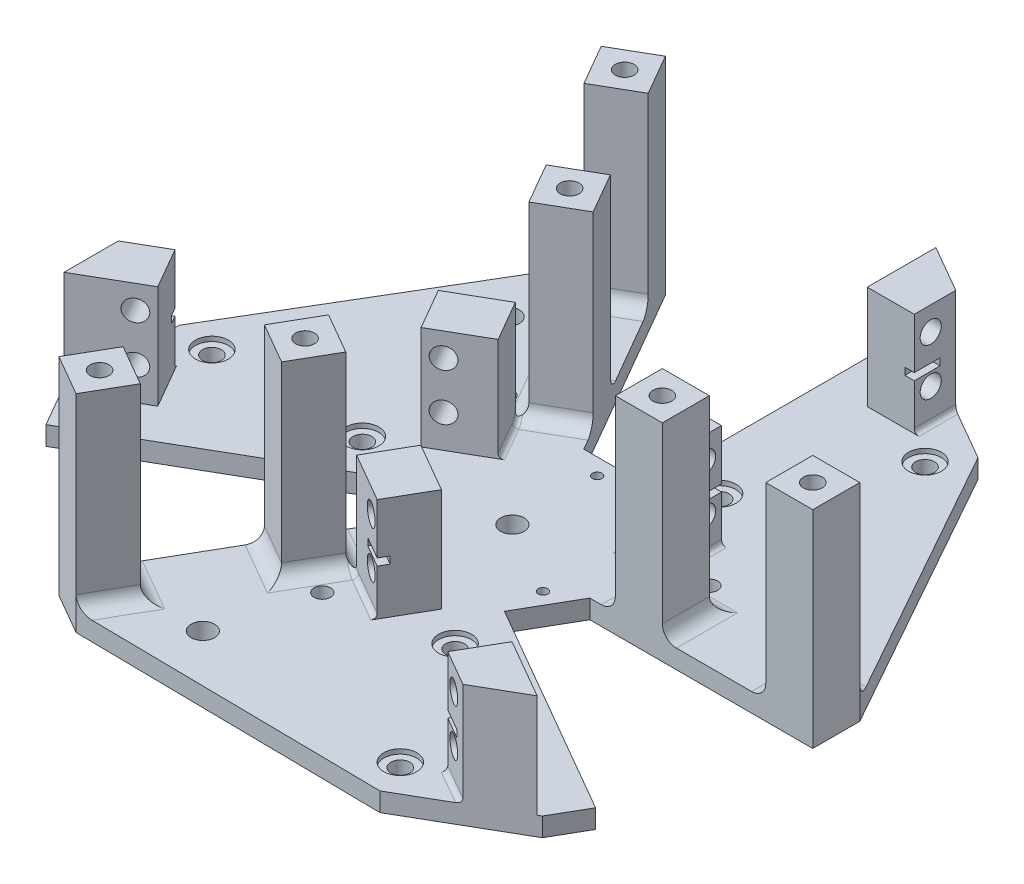
SolidWorks part; units mm, degrees
ref_plane "Front Plane" through (0, 0, 0) normal (0, 0, 1) x (1, 0, 0)
ref_plane "Top Plane" through (0, 0, 0) normal (0, 1, 0) x (1, 0, 0)
ref_plane "Right Plane" through (0, 0, 0) normal (1, 0, 0) x (0, 0, -1)
sketch "Sketch1" plane through (0, 0, 0) normal (0, 1, 0) x (1, 0, 0)
  line L19 (144.3376, 0) -> (72.1688, 125) construction
  line L20 (72.1688, 125) -> (-72.1688, 125) construction
  line L21 (-72.1688, 125) -> (-144.3376, 0) construction
  line L22 (-144.3376, 0) -> (-72.1688, -125) construction
  line L23 (-72.1688, -125) -> (72.1688, -125) construction
  line L24 (72.1688, -125) -> (144.3376, 0) construction
  line L27 (-72.1688, -125) -> (144.3376, 0)
  line L28 (-72.1688, -125) -> (-72.1688, 125)
  line L29 (-72.1688, 125) -> (144.3376, 0)
  circle A1 centre (0, 0) radius 2.5
  circle A22 centre (0, 0) radius 125 construction
  point P16 (0, 0)
  point P22 (0, 0)
  point P23 (0, 0)
  point P27 (0, 0)
  dimension "D1" = 250
  dimension "D2" = 5
extrude "Boss-Extrude1" add sketch "Sketch1" along normal blind 4 contours L20 A1 region at (-68.8616, 0, 0)
sketch "Sketch2" plane through (0, 4, 0) normal (0, 1, 0) x (1, 0, 0)
  line L0 (26, 18.5) -> (26, 6.5)
  line L1 (21, 18.5) -> (21, 59.5) construction
  line L3 (16, 74.0957) -> (16, 59.5)
  line L4 (16, 6.5) -> (26, 6.5)
  line L5 (26, 68.3222) -> (26, 59.5)
  line L26 (16, 18.5) -> (26, 18.5)
  line L28 (16, 59.5) -> (26, 59.5)
  line L29 (16, 18.5) -> (16, 6.5)
  line L50 (-72.1688, 125) -> (144.3376, 0) construction
  line L51 (16, 74.0957) -> (26, 68.3222)
  line L52 (3.0215, -31.7667) -> (-7.3708, -25.7667)
  line L53 (-2.3708, -17.1064) -> (-7.3708, -25.7667)
  line L54 (8.0215, -23.1064) -> (-2.3708, -17.1064)
  line L55 (8.0215, -23.1064) -> (3.0215, -31.7667)
  line L56 (56.1688, -50.9043) -> (43.5285, -43.6064)
  line L57 (43.5285, -43.6064) -> (38.5285, -52.2667)
  line L58 (46.1688, -56.6778) -> (38.5285, -52.2667)
  line L59 (56.1688, -50.9043) -> (46.1688, -56.6778)
  line L60 (-29.0215, 13.2667) -> (-18.6292, 19.2667)
  line L61 (-13.6292, 10.6064) -> (-18.6292, 19.2667)
  line L62 (-24.0215, 4.6064) -> (-13.6292, 10.6064)
  line L63 (-24.0215, 4.6064) -> (-29.0215, 13.2667)
  line L64 (-72.1688, -23.1915) -> (-59.5285, -15.8936)
  line L65 (-59.5285, -15.8936) -> (-64.5285, -7.2333)
  line L66 (-72.1688, -11.6445) -> (-64.5285, -7.2333)
  line L67 (-72.1688, -23.1915) -> (-72.1688, -11.6445)
  dimension "D2" = 16
  dimension "D3" = 3
  dimension "D4" = 10
  dimension "D10" = 41
  dimension "D11" = 12
extrude "Boss-Extrude2" add sketch "Sketch2" along normal blind 22 contours L26 L3 L4 L5 | L3 L28 L5 region at (21, 4, -12.5) region at (20.5891, 4, -65.4731)
sketch "Sketch3" plane through (26, 0, 0) normal (1, 0, 0) x (0, 0, -1)
  line L0 (6.5, 26) -> (6.5, 4) construction
  line L1 (15, 21) -> (63, 21) construction
  line L2 (15, 21) -> (15, 11) construction
  line L3 (15, 11) -> (63, 11) construction
  line L4 (63, 21) -> (63, 11) construction
  line L7 (68.3222, 4) -> (59.5, 4) construction
  circle A0 centre (15, 21) radius 2.25
  circle A1 centre (63, 21) radius 2.25
  circle A2 centre (15, 11) radius 2.25
  circle A3 centre (63, 11) radius 2.25
  dimension "D4" = 4.5
  dimension "D1" = 7
  dimension "D2" = 10
  dimension "D3" = 48
  dimension "D5" = 8.5
extrude "Cut-Extrude1" cut sketch "Sketch3" against normal blind 12 contours A0 | A1 | A2 | A3 region at (26, 21, -15) region at (26, 21, -63) region at (26, 11, -15) region at (26, 11, -63)
sketch "Sketch5" plane through (0, 4, 0) normal (0, 1, 0) x (1, 0, 0)
  line L0 (-72.1688, 1.2882) -> (-14.0152, 34.8632)
  line L1 (-72.1688, -125) -> (-72.1688, 125) construction
  line L2 (0, 0) -> (-15.6126, -8.9581) construction
  line L10 (-72.1688, 125) -> (16, 74.0957) construction
  line L11 (15.2998, 74.5) -> (-72.1688, 125)
  line L12 (-72.1688, 125) -> (-72.1688, 1.2882)
  line L35 (7, 21.5) -> (7, 74.5)
  line L36 (7, 74.5) -> (15.2998, 74.5)
  line L51 (-14.0152, 34.8632) -> (-6.3, 21.5)
  line L52 (-6.3, 21.5) -> (7, 21.5)
  line L53 (0, 0) -> (15.8487, -28.0296) construction
  line L54 (21.7695, -5.294) -> (15.1195, -16.8122)
  line L55 (-30.0152, 62.576) -> (-14.0152, 34.8632)
  line L77 (15.1195, -16.8122) -> (61.0189, -43.3122)
  line L78 (61.0189, -43.3122) -> (56.869, -50.5)
  line L86 (56.869, -50.5) -> (144.3376, 0)
  line L87 (144.3376, 0) -> (37.2, 61.8559)
  line L88 (-30.0152, 62.576) -> (-38.6755, 57.576)
  line L89 (-38.6755, 57.576) -> (-72.1688, 1.2882)
  line L90 (37.2, 61.8559) -> (37.2, -5.294)
  line L91 (37.2, -5.294) -> (21.7695, -5.294)
  line L92 (69.2, -5.294) -> (69.2, 4.706)
  line L93 (69.2, 4.706) -> (37.2, 61.8559)
  line L94 (69.2, -5.294) -> (37.2, -5.294)
  line L95 (-15.4695, -16.206) -> (-22.1195, -4.6878)
  line L96 (-22.1195, -4.6878) -> (-68.0189, -31.1878)
  line L97 (-68.0189, -31.1878) -> (-72.1688, -24)
  line L98 (-72.1688, -24) -> (-72.1688, -125)
  line L99 (-72.1688, -125) -> (34.9688, -63.1441)
  line L100 (34.9688, -63.1441) -> (-23.1848, -29.5691)
  line L101 (-23.1848, -29.5691) -> (-15.4695, -16.206)
  line L102 (-39.1848, -57.2819) -> (-30.5245, -62.2819)
  line L103 (-30.5245, -62.2819) -> (34.9688, -63.1441)
  line L104 (-39.1848, -57.2819) -> (-23.1848, -29.5691)
  circle A0 centre (0, 0) radius 18 construction
  circle A2 centre (-15.6126, -8.9581) radius 1
  circle A3 centre (0.0483, 17.9999) radius 1
  circle A4 centre (15.5642, -9.0418) radius 1
  circle A5 centre (15.8487, -28.0296) radius 2
  circle A6 centre (15.8487, -28.0296) radius 3.5
  circle A7 centre (-32.1987, 0.2894) radius 2
  circle A8 centre (-32.1987, 0.2894) radius 3.5
  circle A9 centre (16.35, 27.7402) radius 2
  circle A10 centre (16.35, 27.7402) radius 3.5
  point P37 (0, 0)
  point P46 (0, 0)
  point P52 (0, 0)
  point P53 (0, 0)
  point P55 (0, 0)
  point P58 (0, 0)
  point P60 (0, 0)
  line M27 (144.3376, 0) -> (26, 68.3222)
  line M28 (-72.1688, 125) -> (-72.1688, -125)
  line M29 (-72.1688, -125) -> (144.3376, 0)
  line M180 (16, 74.0957) -> (-72.1688, 125)
  dimension "D3" = 36
  dimension "D4" = 2
  dimension "D7" = 4
  dimension "D10" = 7
  dimension "D2" = 3
  dimension "D6" = 13.3
  dimension "D8" = 32.2
  dimension "D9" = 32
  dimension "D12" = 10
  dimension "D5" = 3
  dimension "D11" = 3
extrude "Cut-Extrude6" cut sketch "Sketch5" against normal through all contours L55 L51 L52 L35 L36 M180 M28 | M29 M27 | M28 M29 | A7 | A2 | A9 | A5 | A3 | A4 region at (-37.6186, 4, -67.9163) region at (77.6265, 4, 1.3794) region at (-40.0079, 4, 66.5368) region at (-15.6126, 4, 8.9581) region at (15.8487, 4, 28.0296) region at (-32.1987, 4, -0.2894) region at (16.35, 4, -27.7402)
sketch "Sketch20" plane through (0, 4, 0) normal (0, 1, 0) x (1, 0, 0)
  line L4 (-30.0152, 62.576) -> (-25.0152, 53.9157)
  line L5 (-17.6755, 21.2029) -> (-14.0152, 34.8632) construction
  line L6 (-15.8454, 28.033) -> (-24.5056, 23.033) construction
  line L7 (37.2, -5.294) -> (37.2, 4.706)
  line L8 (37.2, -5.294) -> (27.2, -5.294)
  line L9 (27.2, -5.294) -> (27.2, 4.706)
  line L10 (37.2, 4.706) -> (27.2, 4.706)
  line L11 (-23.1848, -29.5691) -> (-14.5245, -34.5691)
  line L12 (-23.1848, -29.5691) -> (-18.1848, -20.9089)
  line L13 (-18.1848, -20.9089) -> (-9.5245, -25.9089)
  line L14 (-14.5245, -34.5691) -> (-9.5245, -25.9089)
  line L17 (-17.6755, 21.2029) -> (-9.0152, 26.2029)
  line L18 (-17.6755, 21.2029) -> (-22.6755, 29.8632)
  line L19 (-9.0152, 26.2029) -> (-14.0152, 34.8632)
  line L20 (-22.6755, 29.8632) -> (-14.0152, 34.8632)
  line L21 (-14.0152, 34.8632) -> (-6.3, 21.5) construction
  line L22 (-30.0152, 62.576) -> (-38.6755, 57.576)
  line L23 (-25.0152, 53.9157) -> (-33.6755, 48.9157)
  line L24 (-38.6755, 57.576) -> (-33.6755, 48.9157)
  line L25 (-30.0152, 62.576) -> (-6.3, 21.5) construction
  line L26 (-30.0152, 62.576) -> (-33.6755, 48.9157) construction
  line L27 (69.2, -5.294) -> (59.2, -5.294)
  line L28 (69.2, -5.294) -> (69.2, 4.706)
  line L29 (69.2, 4.706) -> (59.2, 4.706)
  line L30 (59.2, -5.294) -> (59.2, 4.706)
  line L31 (-39.1848, -57.2819) -> (-34.1848, -48.6217)
  line L32 (-39.1848, -57.2819) -> (-30.5245, -62.2819)
  line L33 (-30.5245, -62.2819) -> (-25.5245, -53.6217)
  line L34 (-34.1848, -48.6217) -> (-25.5245, -53.6217)
  line L35 (-38.6755, 57.576) -> (-72.1688, 1.2882) construction
  circle A0 centre (-15.8454, 28.033) radius 2
  circle A1 centre (-24.5056, 23.033) radius 1.75
  circle A2 centre (32.2, 9.706) radius 1.75
  circle A3 centre (32.2, -0.294) radius 2
  circle A4 centre (-7.6944, -32.739) radius 1.75
  circle A5 centre (-16.3546, -27.739) radius 2
  circle A6 centre (-31.8454, 55.7459) radius 2
  circle A7 centre (64.2, -0.294) radius 2
  circle A8 centre (-32.3546, -55.4518) radius 2
  circle A9 centre (-38.8056, 37.8014) radius 2.5
  circle A10 centre (52.1398, 14.706) radius 2.5
  circle A11 centre (-13.3342, -52.5074) radius 2.5
  point P30 (0, 0)
  point P51 (0, 0)
  line M108 (-6.3, 21.5) -> (-30.0152, 62.576)
  line M155 (69.2, -5.294) -> (69.2, 4.706)
  line M157 (-30.0152, 62.576) -> (-38.6755, 57.576)
  line M162 (-15.4695, -16.206) -> (-39.1848, -57.2819)
  line M163 (-39.1848, -57.2819) -> (-30.5245, -62.2819)
  line M168 (21.7695, -5.294) -> (69.2, -5.294)
  dimension "D3" = 4
  dimension "D4" = 3.5
  dimension "D9" = 4
  dimension "D11" = 5
  dimension "D1" = 10
  dimension "D2" = 10
  dimension "D5" = 10
  dimension "D7" = 10
  dimension "D8" = 10
  dimension "D12" = 20
  dimension "D13" = 10
  dimension "D6" = 3
  dimension "D10" = 3
extrude "Boss-Extrude10" add sketch "Sketch20" along normal blind 40 contours L18 L17 A0 | L10 L9 A3 | L14 L13 A5 | L24 L23 A6 M157 M108 | L30 L29 A7 M168 M155 | L34 L33 A8 M162 M163 region at (-11.6825, 4, -30.4364) region at (-27.6825, 4, -58.1493) region at (32.2, 4, 5.1526) region at (59.3414, 4, 0.294) region at (-20.5175, 4, 25.3356) region at (-29.9512, 4, 51.289)
sketch "Sketch17" plane through (26, 0, 0) normal (1, 0, 0) x (0, 0, -1)
  line L5 (15, 19) -> (15, 9) construction
  line L6 (18.5, 26) -> (18.5, 4) construction
  line L7 (13, 13.75) -> (24, 13.75)
  line L8 (13, 13.75) -> (13, 15.25)
  line L9 (13, 15.25) -> (24, 15.25)
  line L10 (24, 13.75) -> (24, 15.25)
  line L11 (13, 13.75) -> (24, 15.25) construction
  line L12 (13, 15.25) -> (24, 13.75) construction
  line L13 (59.5, 26) -> (59.5, 4) construction
  line L14 (54, 13.75) -> (65, 13.75)
  line L15 (54, 13.75) -> (54, 15.25)
  line L16 (54, 15.25) -> (65, 15.25)
  line L17 (65, 13.75) -> (65, 15.25)
  line L18 (54, 13.75) -> (65, 15.25) construction
  line L19 (54, 15.25) -> (65, 13.75) construction
  point P2 (18.5, 14.5)
  point P11 (59.5, 14.5)
  dimension "D1" = 1.5
  dimension "D2" = 11
  dimension "D3" = 1.5
  dimension "D4" = 11
extrude "Cut-Extrude9" cut sketch "Sketch17" against normal blind 2 contours L9 L8 L7 | L14 L17 L16 L15 | L7 L10 L9 region at (26, 14.5, -18.5) region at (26, 14.5, -59.5)
pattern_circular "CirPattern5" count 3 over 360 about axis through (0, 4, 0) along (0, 1, 0) of "Boss-Extrude2", "Cut-Extrude1", "Cut-Extrude9"
extrude "Cut-Extrude10" cut sketch "Sketch20<3>" against normal blind 10 contours A1 | A0 | A2 | A3 | A4 | A5 | A9 | A10 | A11 region at (-15.8454, 4, -28.033) region at (-24.5056, 4, -23.033) region at (32.2, 4, -9.706) region at (32.2, 4, 0.294) region at (-7.6944, 4, 32.739) region at (-16.3546, 4, 27.739) region at (-38.8056, 4, -37.8014) region at (52.1398, 4, -14.706) region at (-13.3342, 4, 52.5074)
sketch "Sketch20<3>" plane through (0, 4, 0) normal (0, 1, 0) x (1, 0, 0) same geometry as "Sketch20"
extrude "Cut-Extrude11" cut sketch "Sketch5<3>" against normal blind 1 contours A8 A7 | A10 A9 | A6 A5 region at (12.4477, 4, 28.0296) region at (-35.5997, 4, -0.2894) region at (12.949, 4, -27.7402)
sketch "Sketch5<3>" plane through (0, 4, 0) normal (0, 1, 0) x (1, 0, 0) same geometry as "Sketch5"
sketch "Sketch22" plane through (0, 4, 0) normal (0, 1, 0) x (1, 0, 0)
  line L0 (69.2, 4.706) -> (37.2, 61.8559) construction
  line L1 (26, 68.3222) -> (37.2, 61.8559) construction
  circle A1 centre (64.2, -0.294) radius 2 construction
  circle A2 centre (-32.3546, -55.4518) radius 2 construction
  circle A4 centre (64.2, -0.294) radius 2
  circle A5 centre (-32.3546, -55.4518) radius 2
  circle A6 centre (-31.8454, 55.7459) radius 2 construction
  circle A7 centre (-31.8454, 55.7459) radius 2
  circle A8 centre (32.2991, 55.4825) radius 2
  circle A9 centre (32.2991, 55.4825) radius 3.5
  circle A10 centre (31.8459, -55.682) radius 3.5
  circle A11 centre (31.8459, -55.682) radius 2
  circle A12 centre (-64.1988, 0.2927) radius 3.5
  circle A13 centre (-64.1988, 0.2927) radius 2
  point P25 (-0.0179, 0.0311)
  dimension "D3" = 4
  dimension "D4" = 7
  dimension "D1" = 7.39
  dimension "D2" = 7.97
  dimension "D6" = 64.1814
  dimension "D5" = 3
extrude "Cut-Extrude13" cut sketch "Sketch22" against normal blind 10 contours A7 | A4 | A8 | A5 | A11 | A13 region at (64.2, 4, 0.294) region at (-31.8454, 4, -55.7459) region at (32.2991, 4, -55.4825)
sketch "Sketch21" plane through (0, 0, 0) normal (0, -1, 0) x (1, 0, 0)
  line L0 (-17.664, -31.183) -> (-14.0267, -31.183)
  line L1 (35.8373, 0.294) -> (34.0187, 3.444)
  line L2 (34.0187, 3.444) -> (30.3813, 3.444)
  line L3 (30.3813, 3.444) -> (28.5627, 0.294)
  line L4 (28.5627, 0.294) -> (30.3813, -2.856)
  line L5 (30.3813, -2.856) -> (34.0187, -2.856)
  line L6 (34.0187, -2.856) -> (35.8373, 0.294)
  line L7 (-14.0267, -31.183) -> (-12.208, -28.033)
  line L8 (-12.208, -28.033) -> (-14.0267, -24.883)
  line L9 (-14.0267, -24.883) -> (-17.664, -24.883)
  line L10 (-17.664, -24.883) -> (-19.4827, -28.033)
  line L11 (-19.4827, -28.033) -> (-17.664, -31.183)
  line L12 (-18.1733, 30.889) -> (-19.992, 27.739)
  line L13 (-19.992, 27.739) -> (-18.1733, 24.589)
  line L14 (-18.1733, 24.589) -> (-14.536, 24.589)
  line L15 (-14.536, 24.589) -> (-12.7173, 27.739)
  line L16 (-12.7173, 27.739) -> (-14.536, 30.889)
  line L17 (-14.536, 30.889) -> (-18.1733, 30.889)
  line L19 (-33.664, -58.8959) -> (-30.0267, -58.8959)
  line L20 (67.8373, 0.294) -> (66.0187, 3.444)
  line L21 (66.0187, 3.444) -> (62.3813, 3.444)
  line L22 (62.3813, 3.444) -> (60.5627, 0.294)
  line L23 (60.5627, 0.294) -> (62.3813, -2.856)
  line L24 (62.3813, -2.856) -> (66.0187, -2.856)
  line L25 (66.0187, -2.856) -> (67.8373, 0.294)
  line L26 (-30.0267, -58.8959) -> (-28.208, -55.7459)
  line L27 (-28.208, -55.7459) -> (-30.0267, -52.5959)
  line L28 (-30.0267, -52.5959) -> (-33.664, -52.5959)
  line L29 (-33.664, -52.5959) -> (-35.4827, -55.7459)
  line L30 (-35.4827, -55.7459) -> (-33.664, -58.8959)
  line L31 (-34.1733, 58.6018) -> (-35.992, 55.4518)
  line L32 (-35.992, 55.4518) -> (-34.1733, 52.3018)
  line L33 (-34.1733, 52.3018) -> (-30.536, 52.3018)
  line L34 (-30.536, 52.3018) -> (-28.7173, 55.4518)
  line L35 (-28.7173, 55.4518) -> (-30.536, 58.6018)
  line L36 (-30.536, 58.6018) -> (-34.1733, 58.6018)
  circle A0 centre (32.2, 0.294) radius 3.15 construction
  circle A1 centre (64.2, 0.294) radius 3.15 construction
  point P24 (0, 0)
  dimension "D1" = 6.3
  dimension "D3" = 6.3
  dimension "D2" = 3
extrude "Cut-Extrude12" cut sketch "Sketch21" against normal blind 32
extrude "Cut-Extrude14" cut sketch "Sketch22<3>" against normal blind 1 contours A9 A8 | A12 A13 | A10 A11 region at (28.8981, 4, -55.4825) region at (28.4449, 4, 55.682) region at (-67.5998, 4, -0.2927)
sketch "Sketch22<3>" plane through (0, 4, 0) normal (0, 1, 0) x (1, 0, 0) same geometry as "Sketch22"
fillet "Fillet1" radius 3 15 edges at (64.2, 4, -4.706) (32.2, 4, -4.706) (-13.8546, 4, 23.4089) (37.2, 4, 0.294) (-29.8546, 4, 51.1217) (-28.0245, 4, 57.9518) (-12.0245, 4, 30.239) (-13.3454, 4, -23.7029) (-29.3454, 4, -51.4157) (59.2, 4, 0.294) (27.2, 4, 0.294) (-18.8546, 4, 32.0691) (-18.3454, 4, -32.3632) (-20.1755, 4, -25.533) (-36.1755, 4, -53.2459)
fillet "Fillet2" radius 1 15 edges at (-15.6792, 4, -14.1571) (20.1, 4, -6.5) (-4.4208, 4, 20.6571) (-18.0372, 4.0639, -18.2414) (24.8161, 4.0639, -6.5) (-6.7789, 4.0639, 24.7414) (26, 4.0639, -7.0898) (-6.86, 4.0639, 26.0616) (-19.14, 4.0639, -18.9717) (26, 4, -63.9111) (26, 4, -13.103) (42.3486, 4, 54.4722) (-1.6525, 4, 29.0682) (-68.3486, 4, 9.4389) (-24.3475, 4, -15.9652)
